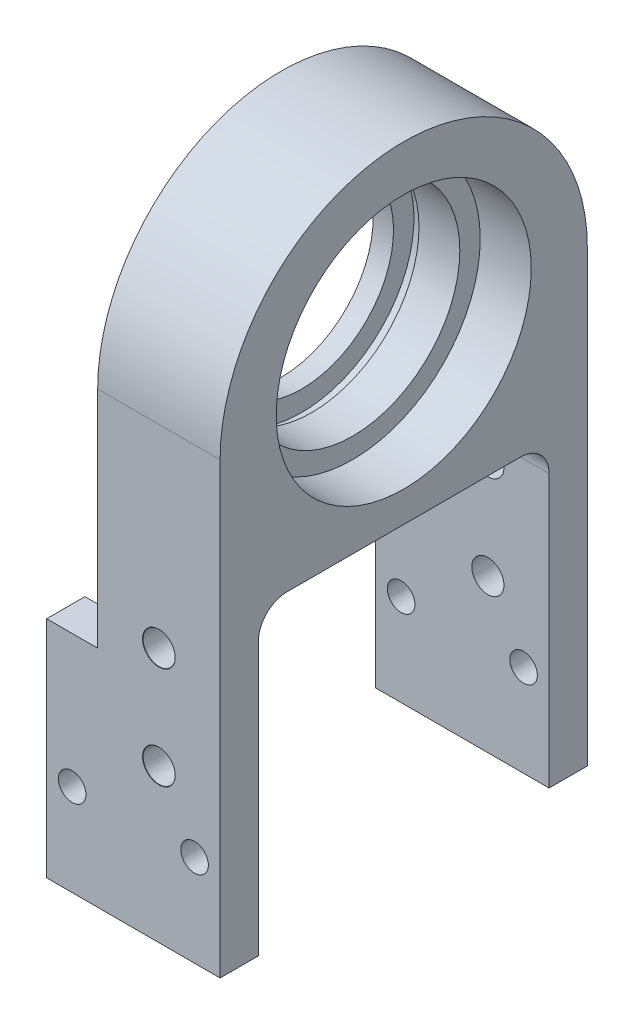
SolidWorks part; units mm, degrees
material "6061 Alloy"
ref_plane "Front Plane" through (0, 0, 0) normal (0, 0, 1) x (1, 0, 0)
ref_plane "Top Plane" through (0, 0, 0) normal (0, 1, 0) x (1, 0, 0)
ref_plane "Right Plane" through (0, 0, 0) normal (1, 0, 0) x (0, 0, -1)
sketch "Sketch1" plane through (0, 0, 0) normal (0, 0, 1) x (1, 0, 0)
  line L0 (0, 0) -> (17, 0)
  line L1 (17, 0) -> (17, 29)
  line L3 (17, 29) -> (17, 62)
  line L4 (17, 62) -> (5, 62)
  line L5 (5, 62) -> (5, 22)
  line L6 (5, 22) -> (0, 22)
  line L7 (0, 22) -> (0, 0)
  dimension "D1" = 17
  dimension "D2" = 62
  dimension "D3" = 22
  dimension "D4" = 12
extrude "Boss-Extrude1" add sketch "Sketch1" along normal blind 36
sketch "Sketch2" plane through (17, 0, 0) normal (1, 0, 0) x (0, 0, -1)
  line L0 (-18, 62) -> (-18, 12.1467) construction
  line L1 (-36, 62) -> (0, 62) construction
  circle A0 centre (-18, 45) radius 10.5
  dimension "D1" = 21
  dimension "D2" = 17
extrude "Cut-Extrude1" cut sketch "Sketch2" against normal through all
sketch "Sketch3" plane through (17, 0, 0) normal (1, 0, 0) x (0, 0, -1)
  line L0 (-36, 0) -> (0, 0) construction
  line L1 (-32.25, 0) -> (-3.75, 0)
  line L2 (-32.25, 0) -> (-32.25, 29.5)
  line L3 (-32.25, 29.5) -> (-3.75, 29.5)
  line L4 (-3.75, 0) -> (-3.75, 29.5)
  line L6 (-18, 0) -> (-18, 45) construction
  dimension "D1" = 28.5
  dimension "D2" = 29.5
extrude "Cut-Extrude2" cut sketch "Sketch3" against normal through all
sketch "Sketch6" plane through (5, 0, 0) normal (-1, 0, 0) x (0, 0, 1)
  circle A0 centre (18, 45) radius 10.5 construction
  circle A1 centre (18, 45) radius 10.5
  circle A2 centre (18, 45) radius 9
  dimension "D1" = 1.5
extrude "Boss-Extrude2" add sketch "Sketch6" against normal blind 2
sketch "Sketch10" plane through (5, 0, 0) normal (-1, 0, 0) x (0, 0, 1)
  circle A0 centre (18, 45) radius 11
  circle A1 centre (18, 45) radius 15
  dimension "D1" = 22
  dimension "D2" = 30
extrude "Cut-Extrude4" cut sketch "Sketch10" against normal blind 0.6
sketch "Sketch11" plane through (17, 0, 0) normal (1, 0, 0) x (0, 0, -1)
  circle A0 centre (-18, 45) radius 12.5
  dimension "D1" = 25
extrude "Cut-Extrude5" cut sketch "Sketch11" against normal blind 5
sketch "Sketch14" plane through (0, 0, 36) normal (0, 0, 1) x (1, 0, 0)
  line L0 (2.5, 9) -> (14.5, 9)
  line L3 (8.5, 9) -> (8.5, 0)
  line L4 (0, 0) -> (17, 0) construction
  line L6 (17, 32.5) -> (17, 57.5) construction
  line L7 (17, 32.5) -> (17, 57.5) construction
  point P0 (14.5, 9)
  point P2 (2.5, 9)
  point P25 (17, 45)
  dimension "D1" = 36
  dimension "D2" = 12
hole_wizard "M2.5 Clearance Hole1" positions "Sketch14" profile "Sketch13" hole size "M2.5" standard "DIN" end condition through all
sketch "Sketch13" plane through (14.5, 9, 36) normal (1, 0, 0) x (0, -1, 0)
  line L0 (0, 0) -> (0, 36)
  line L1 (0, 36) -> (1.35, 36)
  line L2 (1.35, 36) -> (1.35, 0)
  line L5 (1.35, 0) -> (0, 0)
  line L11 (0, -6.35) -> (0, 107.95) construction
  dimension "Thru Hole Dia." = 2.7
  dimension "Thru Hole Depth" = 36
sketch "Sketch16" plane through (0, 0, 0) normal (0, 0, -1) x (-1, 0, 0)
  line L0 (0, 22) -> (-5, 32)
  line L1 (-5, 62) -> (-5, 22) construction
  dimension "D1" = 10
rib "Rib6" [suppressed] sketch "Sketch16" sketch "Sketch16" thickness 3.75 extrusion direction parallel to sketch draft on no parameters "D1"=3.75
sketch "Sketch17" plane through (17, 0, 0) normal (1, 0, 0) x (0, 0, -1)
  line L1 (-36, 62) -> (0, 62)
  line L2 (-36, 62) -> (-36, 45)
  line L3 (-36, 45) -> (0, 45)
  line L4 (0, 62) -> (0, 45)
  circle A0 centre (-18, 45) radius 18
  line M9 (0, 0) -> (0, 62)
  line M10 (0, 62) -> (-36, 62)
  line M11 (-36, 62) -> (-36, 0)
extrude "Cut-Extrude7" cut sketch "Sketch17" against normal through all contours A0 M10 M11 | A0 M9 M10 region at (17, 58.082, 32.7544) region at (17, 58.082, 3.2456)
sketch "Sketch18" plane through (7, 0, 0) normal (1, 0, 0) x (0, 0, -1)
  circle A0 centre (-18, 45) radius 9 construction
  circle A1 centre (-18, 45) radius 9
  circle A2 centre (-18, 45) radius 9.4
  dimension "D1" = 0.4
extrude "Boss-Extrude3" [suppressed] add sketch "Sketch18" along normal up to surface (10 mm away) up to face at (17, 45, 5.5)
sketch "Sketch19" plane through (12, 0, 0) normal (1, 0, 0) x (0, 0, -1)
  circle A0 centre (-18, 45) radius 10.5 construction
  circle A1 centre (-18, 45) radius 10.5
  circle A2 centre (-18, 45) radius 10.9
  dimension "D1" = 0.4
extrude "Boss-Extrude4" [suppressed] add sketch "Sketch19" along normal up to surface (5 mm away) up to face at (17, 45, 5.5)
sketch "Sketch22" plane through (0, 0, 36) normal (0, 0, 1) x (1, 0, 0)
  line L0 (11, 45) -> (11, -8.6789) construction
  line L1 (5, 45) -> (17, 45) construction
  line L2 (0, 0) -> (17, 0) construction
  point P7 (11, 25)
  point P9 (11, 15)
  dimension "D1" = 10
  dimension "D2" = 15
hole_wizard "Tap Drill for M3 Helicoil1" positions "Sketch22" profile "Sketch21" hole size "M3x0.5" standard "DIN" end condition through all
sketch "Sketch21" plane through (11, 15, 36) normal (1, 0, 0) x (0, -1, 0)
  line L0 (0, 0) -> (0, 36)
  line L1 (0, 36) -> (1.575, 36)
  line L2 (1.575, 36) -> (1.575, 0.025)
  line L3 (1.575, 0.025) -> (1.6, 0)
  line L5 (1.6, 0) -> (0, 0)
  line L6 (-1.575, 0.025) -> (-1.6, 0) construction
  line L11 (0, -6.35) -> (0, 107.95) construction
  dimension "Thru Hole Dia." = 3.15
  dimension "Thru Hole Depth" = 36
  dimension "Near C'Sink Dia." = 3.2
  dimension "Near C'Sink Angle" = 90
sketch "Sketch23" plane through (17, 0, 0) normal (1, 0, 0) x (0, 0, -1)
  line L0 (-36, 0) -> (-36, 45) construction
  line L1 (0, 0) -> (0, 45) construction
  line L2 (-23.9161, 62) -> (-12.0839, 62) construction
  line L13 (-36, 45) -> (-36, 0)
  line L14 (-36, 0) -> (-32.25, 0)
  line L15 (-32.25, 0) -> (-32.25, 29.5)
  line L17 (-32.25, 29.5) -> (-3.75, 29.5)
  line L19 (-3.75, 29.5) -> (-3.75, 0)
  line L20 (-3.75, 0) -> (0, 0)
  line L21 (0, 0) -> (0, 45)
  line L22 (-12.0839, 62) -> (-23.9161, 62)
  line L23 (-36, 45) -> (-36, 0)
  line L24 (-36, 0) -> (-32.25, 0)
  line L25 (-32.25, 0) -> (-32.25, 29.5)
  line L27 (-32.25, 29.5) -> (-3.75, 29.5)
  line L29 (-3.75, 29.5) -> (-3.75, 0)
  line L30 (-3.75, 0) -> (0, 0)
  line L31 (0, 0) -> (0, 45)
  line L32 (-12.0839, 62) -> (-23.9161, 62)
  circle A0 centre (-18, 44) radius 18
  arc A3 (-23.9161, 62) -> (-36, 45) centre (-18, 45) ccw
  arc A4 (0, 45) -> (-12.0839, 62) centre (-18, 45) ccw
  arc A5 (-23.9161, 62) -> (-36, 45) centre (-18, 45) ccw
  arc A6 (0, 45) -> (-12.0839, 62) centre (-18, 45) ccw
  arc M15 (-23.9161, 62) -> (-36, 45) centre (-18, 45) ccw
  line M16 (-36, 45) -> (-36, 0)
  arc M25 (0, 45) -> (-12.0839, 62) centre (-18, 45) ccw
  line M26 (-12.0839, 62) -> (-23.9161, 62)
  dimension "D1" = 0
extrude "Cut-Extrude8" cut sketch "Sketch23" against normal through all contours A0 L32 M15 M16 | A0 L31 M25 M26 region at (17, 55.2811, 32.4637) region at (17, 61.9745, 15.042)
sketch "Sketch24" plane through (5, 0, 0) normal (-1, 0, 0) x (0, 0, 1)
  line L0 (3.75, 29.5) -> (32.25, 29.5) construction
  line L1 (13, 29.5) -> (23, 29.5)
  line L2 (13, 29.5) -> (13, 30.8579)
  line L3 (13, 30.8579) -> (23, 30.8579)
  line L4 (23, 29.5) -> (23, 30.8579)
  circle A0 centre (18, 45) radius 15 construction
  dimension "D1" = 10
extrude "Cut-Extrude10" cut sketch "Sketch24" against normal up to surface (0.6 mm away) up to face at (5.6, 34, 18)
fillet "Fillet1" radius 4 2 edges at (5.3, 30.8579, 23) (5.3, 30.8579, 13)
fillet "Fillet2" radius 2.8 2 edges at (11, 29.5, 32.25) (11, 29.5, 3.75)
ref_plane "Plane1" through (0, 0, 18) normal (0, 0, -1) x (-1, 0, 0)
sketch "Sketch25" plane through (0, 0, 18) normal (0, 0, -1) x (-1, 0, 0)
  line L0 (-7, 34.5) -> (-7, 34)
  line L1 (-7, 55.5) -> (-7, 34.5) construction
  line L2 (-7, 34) -> (-8, 34)
  line L3 (-8, 34) -> (-8, 34.5)
  line L4 (-8, 34.5) -> (-7, 34.5)
  line L5 (-5, 45) -> (-19.1096, 45) construction
  line L6 (-5, 36) -> (-5, 54) construction
  dimension "D1" = 1
  dimension "D2" = 0.5
revolve "Cut-Revolve1" cut sketch "Sketch25" angle 360 about L5
